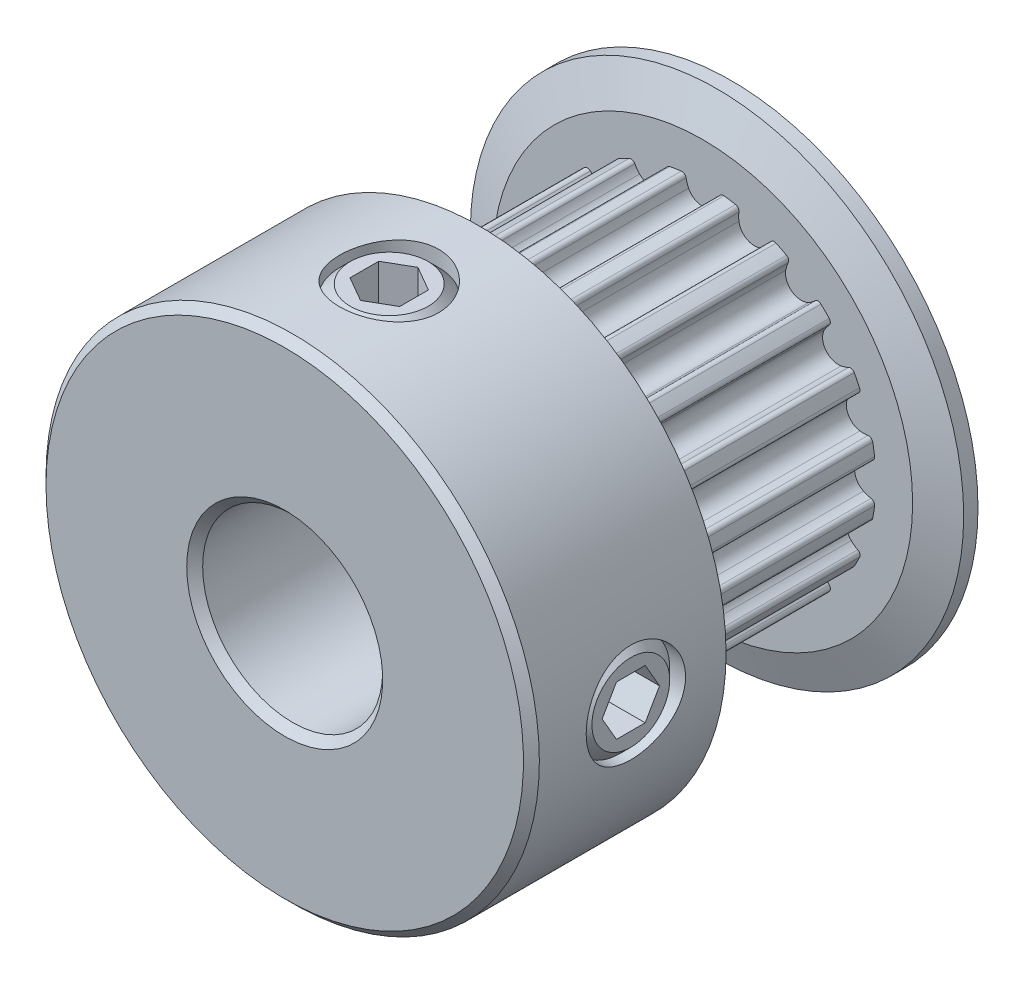
SolidWorks part; units mm, degrees
ref_plane "Front Plane" through (0, 0, 0) normal (0, 0, 1) x (1, 0, 0)
ref_plane "Top Plane" through (0, 0, 0) normal (0, 1, 0) x (1, 0, 0)
ref_plane "Right Plane" through (0, 0, 0) normal (1, 0, 0) x (0, 0, -1)
sketch "Sketch1" plane through (0, 0, 0) normal (0, 0, 1) x (1, 0, 0)
  line L1 (-1.7499, 5.3585) -> (1.7499, 5.3585) construction
  line L4 (0, 0) -> (0, 5.3585) construction
  line L5 (0, 5.3585) -> (0, 11.2113) construction
  line L6 (0, 6.3625) -> (1.9751, 6.0482) construction
  line L7 (1.9751, 6.0482) -> (2.6648, 5.8229) construction
  line L8 (1.9751, 6.0482) -> (1.7499, 5.3585) construction
  line L9 (-1.9751, 6.0482) -> (-1.7499, 5.3585) construction
  line L10 (-1.8963, 5.8067) -> (-2.841, 8.6995)
  line L11 (-2.841, 8.6995) -> (2.841, 8.6995)
  line L12 (2.841, 8.6995) -> (1.8963, 5.8067)
  circle A0 centre (0, 0) radius 6.3625 construction
  circle A1 centre (0, 0) radius 8.6995 construction
  circle A2 centre (0, 0) radius 6.1085 construction
  arc A3 (-0.4989, 5.6703) -> (0.4989, 5.6703) centre (0, 5.9135) ccw
  arc A4 (-0.4989, 5.6703) -> (-0.5855, 5.9387) centre (0.4, 6.1085) cw
  arc A5 (-1.8963, 5.8067) -> (-0.7518, 6.0621) centre (0, 0) cw
  arc A6 (-0.5855, 5.9387) -> (-0.7518, 6.0621) centre (-0.7333, 5.9132) ccw
  arc A7 (1.8963, 5.8067) -> (0.7518, 6.0621) centre (0, 0) ccw
  arc A8 (0.5855, 5.9387) -> (0.7518, 6.0621) centre (0.7333, 5.9132) cw
  arc A9 (0.4989, 5.6703) -> (0.5855, 5.9387) centre (-0.4, 6.1085) ccw
  point P6 (0, 20.9083)
  point P11 (0, 6.3625)
  point P13 (0, 8.6995)
  point P14 (0, 6.1085)
  dimension "D1" = 9.697
  dimension "D2" = 4.8488
sketch "Sketch2" plane through (0, 0, 0) normal (1, 0, 0) x (0, 0, -1)
  line L0 (-7.875, 3.175) -> (7.875, 3.175)
  line L1 (-7.875, 3.175) -> (-7.875, 8.6995)
  line L2 (-1.01, 8.6995) -> (-7.875, 8.6995)
  line L3 (-1.515, 3.175) -> (-1.515, 8.6995) construction
  line L4 (-1.515, 8.6995) -> (-0.505, 8.6995) construction
  line L5 (-0.505, 8.6995) -> (-0.505, 6.1085) construction
  line L6 (-0.505, 6.1085) -> (6.865, 6.1085)
  line L7 (6.865, 6.1085) -> (6.865, 8.6995) construction
  line L8 (6.865, 8.6995) -> (7.875, 8.6995) construction
  line L9 (7.875, 8.6995) -> (7.875, 3.175)
  line L10 (-7.875, 0) -> (7.875, 0) construction
  line L11 (7.37, 8.6995) -> (6.865, 7.404)
  line L12 (-0.505, 7.404) -> (-1.01, 8.6995)
  line L14 (-0.505, 7.404) -> (-0.505, 6.1085)
  line L15 (6.865, 6.1085) -> (6.865, 7.404)
  line L16 (7.37, 8.6995) -> (7.875, 8.6995)
  arc A0 (-0.505, 7.404) -> (-1.01, 8.6995) centre (-2.4192, 7.404) ccw construction
  arc A1 (6.865, 7.404) -> (7.37, 8.6995) centre (8.7792, 7.404) cw construction
  point P12 (-0.505, 7.404)
  point P14 (-1.01, 8.6995)
  point P20 (6.865, 7.404)
  point P21 (7.37, 8.6995)
  point P25 (6.865, 0)
  point P26 (-0.505, 0)
  dimension "OA" = 15.75
  dimension "Bore" = 6.35
  dimension "Outside Width" = 8.38
  dimension "Inside Width" = 7.37
revolve "Revolve1" add sketch "Sketch2" angle 360 mid plane about L10
sketch "Sketch3" plane through (0, 0, 0) normal (0, 0, 1) x (1, 0, 0)
  line L6 (2.841, 8.6995) -> (-2.841, 8.6995)
  line L7 (1.8963, 5.8067) -> (2.841, 8.6995)
  line L8 (-2.841, 8.6995) -> (-1.8963, 5.8067)
  line L9 (2.841, 8.6995) -> (-2.841, 8.6995)
  line L10 (1.8963, 5.8067) -> (2.841, 8.6995)
  line L11 (-2.841, 8.6995) -> (-1.8963, 5.8067)
  arc A8 (1.8963, 5.8067) -> (0.7518, 6.0621) centre (0, 0) ccw
  arc A9 (0.7518, 6.0621) -> (0.5855, 5.9387) centre (0.7333, 5.9132) ccw
  arc A10 (0.4989, 5.6703) -> (0.5855, 5.9387) centre (-0.4, 6.1085) ccw
  arc A11 (-0.4989, 5.6703) -> (0.4989, 5.6703) centre (0, 5.9135) ccw
  arc A12 (-0.5855, 5.9387) -> (-0.4989, 5.6703) centre (0.4, 6.1085) ccw
  arc A13 (-0.5855, 5.9387) -> (-0.7518, 6.0621) centre (-0.7333, 5.9132) ccw
  arc A14 (-0.7518, 6.0621) -> (-1.8963, 5.8067) centre (0, 0) ccw
  arc A15 (1.8963, 5.8067) -> (0.7518, 6.0621) centre (0, 0) ccw
  arc A16 (0.7518, 6.0621) -> (0.5855, 5.9387) centre (0.7333, 5.9132) ccw
  arc A17 (0.4989, 5.6703) -> (0.5855, 5.9387) centre (-0.4, 6.1085) ccw
  arc A18 (-0.4989, 5.6703) -> (0.4989, 5.6703) centre (0, 5.9135) ccw
  arc A19 (-0.5855, 5.9387) -> (-0.4989, 5.6703) centre (0.4, 6.1085) ccw
  arc A20 (-0.5855, 5.9387) -> (-0.7518, 6.0621) centre (-0.7333, 5.9132) ccw
  arc A21 (-0.7518, 6.0621) -> (-1.8963, 5.8067) centre (0, 0) ccw
  dimension "D1" = 0
extrude "Cut-Extrude1" cut sketch "Sketch3" against normal up to vertex (6.865 mm away) from vertex up to point (0, 6.1085, -6.865) starting at point (0, 6.1085, 0.505)
pattern_circular "CirPattern1" count 20 over 360 about axis through (0, 0, 7.875) along (0, 0, 1) of "Cut-Extrude1"
sketch "Sketch4" plane through (0, 0, 0) normal (1, 0, 0) x (0, -1, 0)
  line L0 (0, -0.505) -> (0, -7.875) construction
  line L1 (-3.175, -7.875) -> (3.175, -7.875) construction
  line L2 (7.404, -0.505) -> (-7.404, -0.505) construction
  circle A0 centre (0, -4.19) radius 1.7526
extrude "Cut-Extrude2" cut sketch "Sketch4" along normal through all
ref_plane "Plane1" through (0, 0, 4.19) normal (0, 0, 1) x (1, 0, 0)
sketch "Sketch5" plane through (0, 0, 4.19) normal (0, 0, 1) x (1, 0, 0)
  line L0 (0, 0) -> (0, 8.6995) construction
  line L1 (3.175, -1.3716) -> (3.175, 0)
  line L2 (3.556, -1.7526) -> (8.1401, -1.7526)
  line L3 (3.175, 0) -> (8.6995, 0) construction
  line L4 (3.175, 0) -> (8.5211, 0)
  line L5 (8.5211, 0) -> (8.5211, -1.3716)
  line L6 (3.556, -1.7526) -> (3.175, -1.3716)
  line L7 (8.5211, -1.3716) -> (8.1401, -1.7526)
  circle A0 centre (0, 0) radius 8.6995 construction
  circle A1 centre (0, 0) radius 3.175 construction
  point P2 (3.175, -1.7526)
  point P11 (8.5211, -1.7526)
revolve "Revolve2" add sketch "Sketch5" angle 360 mid plane about L4
sketch "Sketch6" plane through (8.5211, 5.3841, 0) normal (-1, 0, 0) x (0, -1, 0)
  line L1 (5.3841, 5.2019) -> (4.5078, 4.6959)
  line L2 (4.5078, 4.6959) -> (4.5078, 3.6841)
  line L3 (4.5078, 3.6841) -> (5.3841, 3.1781)
  line L4 (5.3841, 3.1781) -> (6.2604, 3.6841)
  line L5 (6.2604, 3.6841) -> (6.2604, 4.6959)
  line L6 (6.2604, 4.6959) -> (5.3841, 5.2019)
  circle A0 centre (5.3841, 4.19) radius 0.8763 construction
  dimension "D1" = 1.7526
extrude "Cut-Extrude3" cut sketch "Sketch6" along normal blind 1.3144
pattern_circular "CirPattern3" count 2 over 90 about axis through (0, 0, 7.875) along (0, 0, 1) of "Cut-Extrude2", "Revolve2", "Cut-Extrude3"
chamfer "Chamfer1" distance 0.2807 angle 45 2 edges at (3.175, 0, 7.875) (8.6995, 0, 7.875)
ref_axis "Center Axis 1" through (0, 0, -7.875) along (0, 0, 1)
ref_plane "Contact Plane 1" through (0, 0, 7.875) normal (0, 0, 1) x (1, 0, 0)
ref_plane "Contact Plane 2" through (0, 0, -7.875) normal (0, 0, -1) x (-1, 0, 0)
equation "\"D2@Sketch1\"= \"D1@Sketch1\" / 2"
equation "\"D1@Sketch6\" = \"Set Screw@Sketch4\" / 2"
equation "\"D1@Cut-Extrude3\" = \"D1@Sketch6\"*.75"
